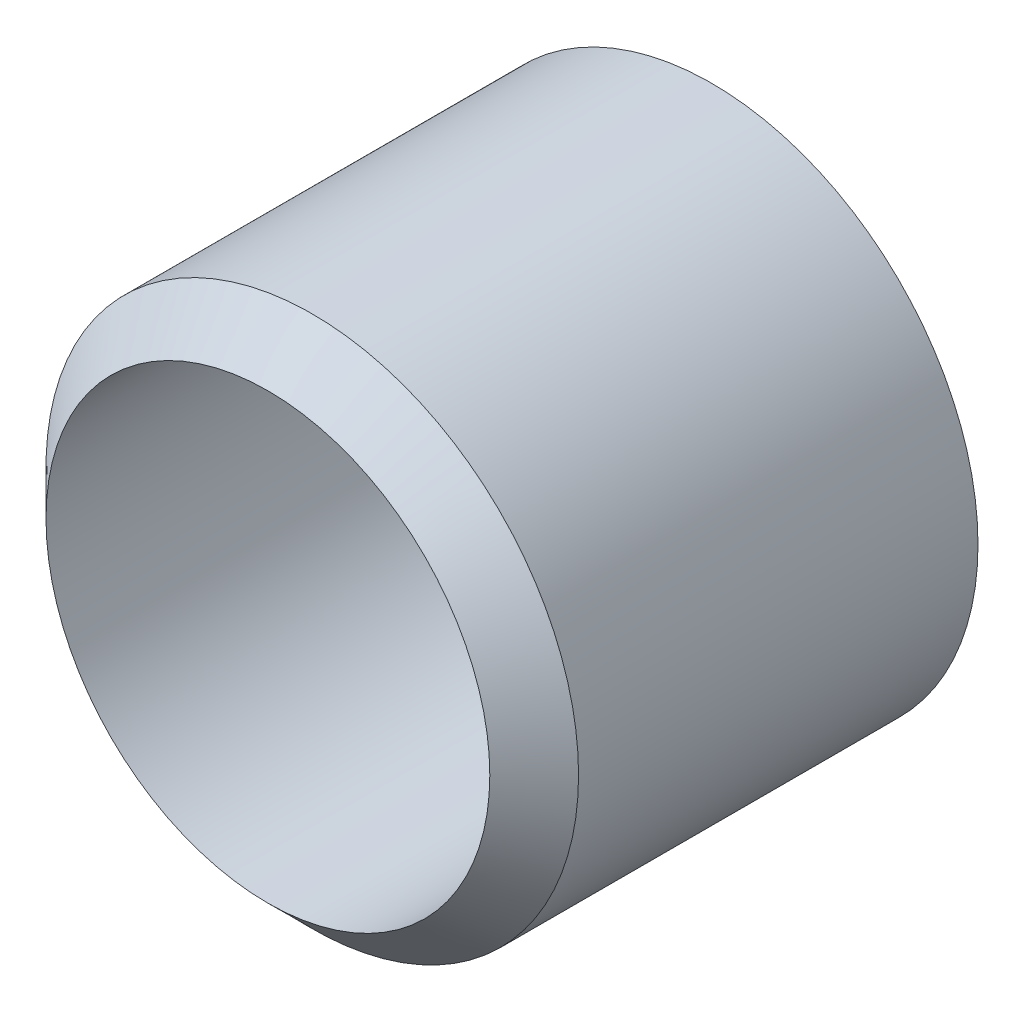
SolidWorks part; units mm, degrees
material "6061 Alloy"
ref_plane "Front" through (0, 0, 0) normal (0, 0, 1) x (1, 0, 0)
ref_plane "Top" through (0, 0, 0) normal (0, 1, 0) x (1, 0, 0)
ref_plane "Right" through (0, 0, 0) normal (1, 0, 0) x (0, 0, -1)
sketch "Sketch2" plane through (0, 0, 0) normal (0, 0, 1) x (1, 0, 0)
  circle A0 centre (0, 0) radius 250
  circle A1 centre (0, 0) radius 300
  dimension "D1" = 500
  dimension "D2" = 600
extrude "Boss-Extrude1" add sketch "Sketch2" along normal blind 500
fillet "Chamfer1" radius 50 1 edges at (300, 0, 500) profile chamfer
